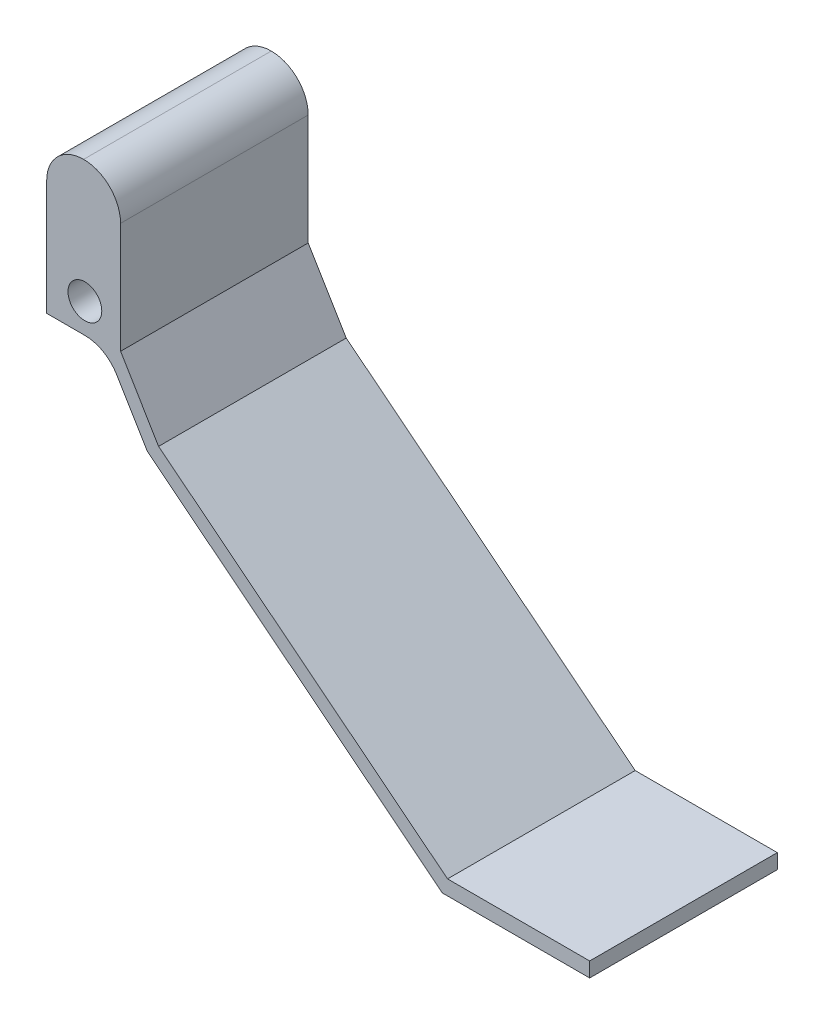
SolidWorks part; units mm, degrees
ref_plane "Front Plane" through (0, 0, 0) normal (0, 0, 1) x (1, 0, 0)
ref_plane "Top Plane" through (0, 0, 0) normal (0, 1, 0) x (1, 0, 0)
ref_plane "Right Plane" through (0, 0, 0) normal (1, 0, 0) x (0, 0, -1)
sketch "Sketch1" plane through (0, 0, 0) normal (0, 0, 1) x (1, 0, 0)
  line L0 (0, 0) -> (5.1477, -8.5733)
  line L1 (-2, -0.5543) -> (-10, -0.5543)
  line L2 (5.1477, -8.5733) -> (44.2613, -39.7201)
  line L3 (0, 0) -> (0, 20)
  line L4 (-2, -0.5543) -> (3.6191, -9.9127)
  line L5 (44.2613, -39.7201) -> (63.5, -39.7201)
  line L6 (3.6191, -9.9127) -> (43.5623, -41.7201)
  line L7 (43.5623, -41.7201) -> (63.5, -41.7201)
  line L8 (-2, -0.5543) -> (-2, 20) construction
  line L9 (0, 20) -> (-10, 20)
  line L10 (-10, 20) -> (-10, -0.5543)
  line L11 (63.5, -39.7201) -> (63.5, -41.7201)
  dimension "D1" = 10
  dimension "D2" = 2
  dimension "D3" = 50
  dimension "D4" = 20
  dimension "D5" = 8
extrude "Boss-Extrude1" add sketch "Sketch1" along normal blind 25.4 contours L10 L1 L4 L6 L7 L11 L5 L2 L0 L3 L9
fillet "Fillet1" radius 5 1 edges at (-2, -0.5543, 12.7)
sketch "Sketch2" plane through (0, 0, 25.4) normal (0, 0, 1) x (1, 0, 0)
  line L0 (-4.8299, -0.5543) -> (-4.8299, 3.4457)
  circle A0 centre (-4.8299, 3.4457) radius 2.286
  dimension "D2" = 4.572
  dimension "D1" = 4
fillet "Fillet2" radius 5 1 edges at (0, 20, 12.7)
fillet "Fillet3" radius 5 1 edges at (-10, 20, 12.7)
ref_plane "Plane1" through (0, 0, 12.7) normal (0, 0, -1) x (-1, 0, 0)
extrude "Cut-Extrude2" cut sketch "Sketch2" against normal through all contours A0
